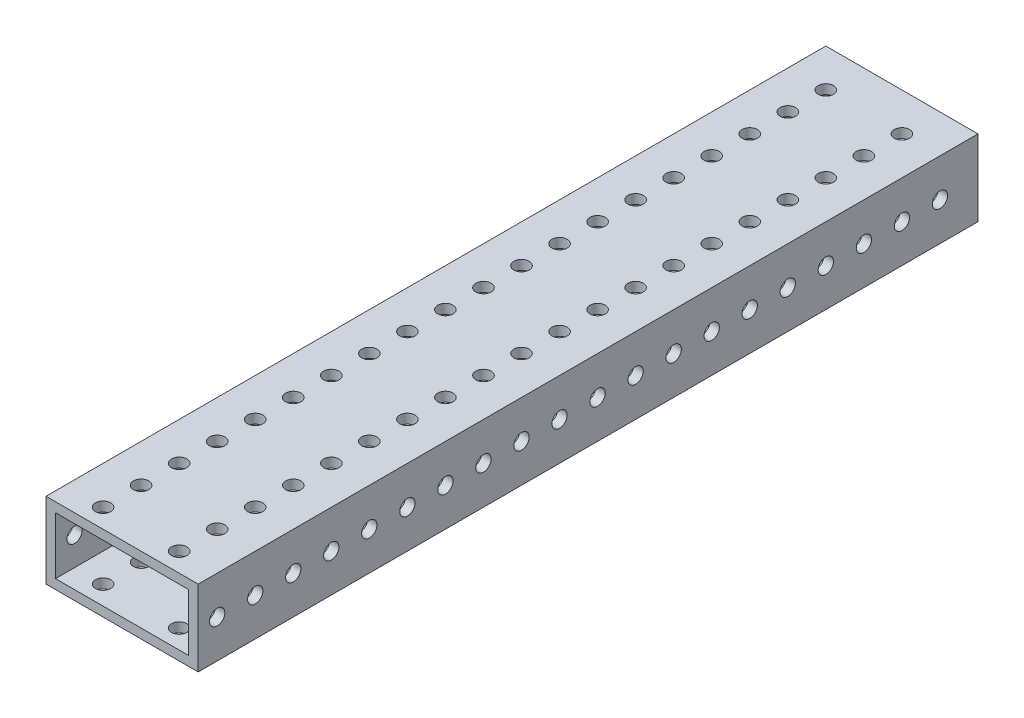
SolidWorks part; units mm, degrees
material "6061-T6 (SS)"
ref_plane "Front Plane" through (0, 0, 0) normal (0, 0, 1) x (1, 0, 0)
ref_plane "Top Plane" through (0, 0, 0) normal (0, 1, 0) x (1, 0, 0)
ref_plane "Right Plane" through (0, 0, 0) normal (1, 0, 0) x (0, 0, -1)
sketch "Sketch1" plane through (0, 0, 0) normal (0, 0, 1) x (1, 0, 0)
  line L0 (-22.225, 9.525) -> (22.225, 9.525)
  line L1 (-25.4, 12.7) -> (25.4, 12.7)
  line L2 (-25.4, 12.7) -> (-25.4, -12.7)
  line L3 (-25.4, -12.7) -> (25.4, -12.7)
  line L4 (25.4, 12.7) -> (25.4, -12.7)
  line L5 (22.225, 9.525) -> (22.225, -9.525)
  line L6 (-22.225, -9.525) -> (22.225, -9.525)
  line L7 (-22.225, 9.525) -> (-22.225, -9.525)
  line L8 (-25.4, 12.7) -> (25.4, -12.7) construction
  line L9 (25.4, 12.7) -> (-25.4, -12.7) construction
  point P5 (0, 0)
  dimension "D1" = 50.8
  dimension "D2" = 25.4
  dimension "D3" = 3.175
extrude "Boss-Extrude1" add sketch "Sketch1" along normal mid plane 368.3
sketch "Sketch5" plane through (-25.4, 0, 0) normal (-1, 0, 0) x (0, 0, 1)
  line L0 (184.15, -12.7) -> (-184.15, -12.7) construction
  line L1 (-184.15, 12.7) -> (-120.65, 12.7)
  line L2 (-184.15, 12.7) -> (-184.15, -12.7)
  line L3 (-184.15, -12.7) -> (-120.65, -12.7)
  line L4 (-120.65, 12.7) -> (-120.65, -12.7)
  dimension "D1" = 63.5
sketch "Sketch6" plane through (25.4, 0, 0) normal (1, 0, 0) x (0, 0, -1)
  line L0 (-184.15, -12.7) -> (-184.15, 12.7) construction
  line L1 (-184.15, 12.7) -> (184.15, 12.7) construction
  circle A0 centre (-177.8, 0) radius 2.5527
  circle A1 centre (-165.1, 0) radius 2.5527
  circle A2 centre (-152.4, 0) radius 2.5527
  circle A3 centre (-139.7, 0) radius 2.5527
  circle A4 centre (-127, 0) radius 2.5527
  circle A5 centre (-114.3, 0) radius 2.5527
  circle A6 centre (-101.6, 0) radius 2.5527
  circle A7 centre (-88.9, 0) radius 2.5527
  circle A8 centre (-76.2, 0) radius 2.5527
  circle A9 centre (-63.5, 0) radius 2.5527
  circle A10 centre (-50.8, 0) radius 2.5527
  circle A11 centre (-38.1, 0) radius 2.5527
  circle A12 centre (-25.4, 0) radius 2.5527
  circle A13 centre (-12.7, 0) radius 2.5527
  circle A14 centre (0, 0) radius 2.5527
  circle A15 centre (12.7, 0) radius 2.5527
  circle A16 centre (25.4, 0) radius 2.5527
  circle A17 centre (38.1, 0) radius 2.5527
  circle A18 centre (50.8, 0) radius 2.5527
  circle A19 centre (63.5, 0) radius 2.5527
  circle A20 centre (76.2, 0) radius 2.5527 construction
  circle A21 centre (88.9, 0) radius 2.5527
  circle A22 centre (101.6, 0) radius 2.5527
  circle A23 centre (114.3, 0) radius 2.5527 construction
  circle A24 centre (127, 0) radius 2.5527 construction
  circle A25 centre (139.7, 0) radius 2.5527 construction
  circle A26 centre (152.4, 0) radius 2.5527 construction
  circle A27 centre (165.1, 0) radius 2.5527 construction
  circle A28 centre (177.8, 0) radius 2.5527 construction
  dimension "D1" = 6.35
  dimension "D2" = 12.7
  dimension "D3" = 5.1054
  dimension "D4" = 29
extrude "Cut-Extrude5" cut sketch "Sketch6" against normal through all
extrude "Cut-Extrude6" cut sketch "Sketch5" against normal through all
sketch "Sketch2" plane through (0, 12.7, 0) normal (0, 1, 0) x (1, 0, 0)
  line L0 (25.4, -184.15) -> (-25.4, -184.15) construction
  line L1 (-25.4, -184.15) -> (-25.4, 120.65) construction
  line L4 (25.4, 184.15) -> (-25.4, 184.15) construction
  circle A0 centre (12.7, -177.8) radius 2.5527
  circle A1 centre (25.4, -171.45) radius 2.5527 construction
  circle A2 centre (-12.7, -177.8) radius 2.5527
  circle A3 centre (-12.7, -165.1) radius 2.5527
  circle A4 centre (12.7, -165.1) radius 2.5527 construction
  circle A5 centre (25.4, -158.75) radius 2.5527 construction
  circle A6 centre (-12.7, -152.4) radius 2.5527
  circle A7 centre (12.7, -152.4) radius 2.5527 construction
  circle A8 centre (25.4, -146.05) radius 2.5527 construction
  circle A9 centre (-12.7, -139.7) radius 2.5527
  circle A10 centre (12.7, -139.7) radius 2.5527 construction
  circle A11 centre (25.4, -133.35) radius 2.5527 construction
  circle A12 centre (-12.7, -127) radius 2.5527
  circle A13 centre (12.7, -127) radius 2.5527 construction
  circle A14 centre (25.4, -120.65) radius 2.5527 construction
  circle A15 centre (-12.7, -114.3) radius 2.5527
  circle A16 centre (12.7, -114.3) radius 2.5527 construction
  circle A17 centre (25.4, -107.95) radius 2.5527 construction
  circle A18 centre (-12.7, -101.6) radius 2.5527
  circle A19 centre (12.7, -101.6) radius 2.5527 construction
  circle A20 centre (25.4, -95.25) radius 2.5527 construction
  circle A21 centre (-12.7, -88.9) radius 2.5527
  circle A22 centre (12.7, -88.9) radius 2.5527 construction
  circle A23 centre (25.4, -82.55) radius 2.5527 construction
  circle A24 centre (-12.7, -76.2) radius 2.5527
  circle A25 centre (12.7, -76.2) radius 2.5527 construction
  circle A26 centre (25.4, -69.85) radius 2.5527 construction
  circle A27 centre (-12.7, -63.5) radius 2.5527
  circle A28 centre (12.7, -63.5) radius 2.5527 construction
  circle A29 centre (25.4, -57.15) radius 2.5527 construction
  circle A30 centre (-12.7, -50.8) radius 2.5527
  circle A31 centre (12.7, -50.8) radius 2.5527 construction
  circle A32 centre (25.4, -44.45) radius 2.5527 construction
  circle A33 centre (-12.7, -38.1) radius 2.5527
  circle A34 centre (12.7, -38.1) radius 2.5527 construction
  circle A35 centre (25.4, -31.75) radius 2.5527 construction
  circle A36 centre (-12.7, -25.4) radius 2.5527
  circle A37 centre (12.7, -25.4) radius 2.5527 construction
  circle A38 centre (25.4, -19.05) radius 2.5527 construction
  circle A39 centre (-12.7, -12.7) radius 2.5527
  circle A40 centre (12.7, -12.7) radius 2.5527 construction
  circle A41 centre (25.4, -6.35) radius 2.5527 construction
  circle A42 centre (-12.7, 0) radius 2.5527
  circle A43 centre (12.7, 0) radius 2.5527 construction
  circle A44 centre (25.4, 6.35) radius 2.5527 construction
  circle A45 centre (-12.7, 12.7) radius 2.5527
  circle A46 centre (12.7, 12.7) radius 2.5527 construction
  circle A47 centre (25.4, 19.05) radius 2.5527 construction
  circle A48 centre (-12.7, 25.4) radius 2.5527
  circle A49 centre (12.7, 25.4) radius 2.5527 construction
  circle A50 centre (25.4, 31.75) radius 2.5527 construction
  circle A51 centre (-12.7, 38.1) radius 2.5527
  circle A52 centre (12.7, 38.1) radius 2.5527 construction
  circle A53 centre (25.4, 44.45) radius 2.5527 construction
  circle A54 centre (-12.7, 50.8) radius 2.5527
  circle A55 centre (12.7, 50.8) radius 2.5527 construction
  circle A56 centre (25.4, 57.15) radius 2.5527 construction
  circle A57 centre (-12.7, 63.5) radius 2.5527
  circle A58 centre (12.7, 63.5) radius 2.5527 construction
  circle A59 centre (25.4, 69.85) radius 2.5527 construction
  circle A60 centre (-12.7, 76.2) radius 2.5527 construction
  circle A61 centre (12.7, 76.2) radius 2.5527 construction
  circle A62 centre (25.4, 82.55) radius 2.5527 construction
  circle A63 centre (-12.7, 88.9) radius 2.5527
  circle A64 centre (12.7, 88.9) radius 2.5527 construction
  circle A65 centre (25.4, 95.25) radius 2.5527 construction
  circle A66 centre (-12.7, 101.6) radius 2.5527
  circle A67 centre (12.7, 101.6) radius 2.5527 construction
  circle A68 centre (25.4, 107.95) radius 2.5527 construction
  circle A69 centre (-12.7, 114.3) radius 2.5527 construction
  circle A70 centre (12.7, 114.3) radius 2.5527 construction
  circle A71 centre (25.4, 120.65) radius 2.5527 construction
  circle A72 centre (-12.7, 127) radius 2.5527 construction
  circle A73 centre (12.7, 127) radius 2.5527 construction
  circle A74 centre (25.4, 133.35) radius 2.5527 construction
  circle A75 centre (-12.7, 139.7) radius 2.5527
  circle A76 centre (12.7, 139.7) radius 2.5527 construction
  circle A77 centre (25.4, 146.05) radius 2.5527 construction
  circle A78 centre (-12.7, 152.4) radius 2.5527
  circle A79 centre (12.7, 152.4) radius 2.5527 construction
  circle A80 centre (25.4, 158.75) radius 2.5527 construction
  circle A81 centre (-12.7, 165.1) radius 2.5527
  circle A82 centre (12.7, 165.1) radius 2.5527 construction
  circle A83 centre (25.4, 171.45) radius 2.5527 construction
  circle A84 centre (-12.7, 177.8) radius 2.5527 construction
  circle A85 centre (12.7, 177.8) radius 2.5527 construction
  circle A86 centre (25.4, 184.15) radius 2.5527 construction
  circle A87 centre (-12.7, 190.5) radius 2.5527
  circle A88 centre (12.7, 190.5) radius 2.5527 construction
  circle A89 centre (25.4, 196.85) radius 2.5527 construction
  circle A90 centre (-12.7, 203.2) radius 2.5527
  circle A91 centre (12.7, 203.2) radius 2.5527 construction
  circle A92 centre (25.4, 209.55) radius 2.5527 construction
  circle A93 centre (-12.7, 215.9) radius 2.5527
  circle A94 centre (12.7, 215.9) radius 2.5527 construction
  circle A95 centre (25.4, 222.25) radius 2.5527 construction
  circle A96 centre (-12.7, 228.6) radius 2.5527
  circle A97 centre (12.7, 228.6) radius 2.5527 construction
  circle A98 centre (25.4, 234.95) radius 2.5527 construction
  circle A99 centre (-12.7, 241.3) radius 2.5527
  circle A100 centre (12.7, 241.3) radius 2.5527 construction
  circle A101 centre (25.4, 247.65) radius 2.5527 construction
  circle A108 centre (-12.7, 266.7) radius 2.5527 [skipped]
  circle A109 centre (12.7, 266.7) radius 2.5527 [skipped]
  circle A110 centre (25.4, 273.05) radius 2.5527 [skipped]
  circle A111 centre (-12.7, 254) radius 2.5527 [skipped]
  circle A112 centre (12.7, 254) radius 2.5527 [skipped]
  circle A113 centre (25.4, 260.35) radius 2.5527 [skipped]
  circle A114 centre (25.4, 260.35) radius 2.5527 construction
  circle A115 centre (12.7, 254) radius 2.5527 construction
  circle A116 centre (-12.7, 254) radius 2.5527
  circle A117 centre (25.4, 273.05) radius 2.5527 construction
  circle A118 centre (12.7, 266.7) radius 2.5527 construction
  circle A119 centre (-12.7, 266.7) radius 2.5527
  circle A120 centre (25.4, 285.75) radius 2.5527 construction
  circle A121 centre (12.7, 279.4) radius 2.5527 construction
  circle A122 centre (-12.7, 279.4) radius 2.5527
  circle A123 centre (25.4, 298.45) radius 2.5527 construction
  circle A124 centre (12.7, 292.1) radius 2.5527 construction
  circle A125 centre (-12.7, 292.1) radius 2.5527
  circle A126 centre (25.4, 311.15) radius 2.5527 construction
  circle A127 centre (12.7, 304.8) radius 2.5527 construction
  circle A128 centre (-12.7, 304.8) radius 2.5527
  circle A129 centre (25.4, 323.85) radius 2.5527 construction
  circle A130 centre (12.7, 317.5) radius 2.5527 construction
  circle A131 centre (-12.7, 317.5) radius 2.5527
  circle A132 centre (25.4, 336.55) radius 2.5527 construction
  circle A133 centre (12.7, 330.2) radius 2.5527 construction
  circle A134 centre (-12.7, 330.2) radius 2.5527
  circle A135 centre (25.4, 349.25) radius 2.5527 construction
  circle A136 centre (12.7, 342.9) radius 2.5527 construction
  circle A137 centre (-12.7, 342.9) radius 2.5527
  circle A138 centre (25.4, 361.95) radius 2.5527 construction
  circle A139 centre (12.7, 355.6) radius 2.5527 construction
  circle A140 centre (-12.7, 355.6) radius 2.5527
  circle A141 centre (25.4, 374.65) radius 2.5527 construction
  circle A142 centre (12.7, 368.3) radius 2.5527 construction
  circle A143 centre (-12.7, 368.3) radius 2.5527
  circle A144 centre (25.4, 387.35) radius 2.5527 construction
  circle A145 centre (12.7, 381) radius 2.5527 construction
  circle A146 centre (-12.7, 381) radius 2.5527
  circle A147 centre (25.4, 400.05) radius 2.5527 construction
  circle A148 centre (12.7, 393.7) radius 2.5527 construction
  circle A149 centre (-12.7, 393.7) radius 2.5527
  circle A150 centre (25.4, 412.75) radius 2.5527 construction
  circle A151 centre (12.7, 406.4) radius 2.5527 construction
  circle A152 centre (-12.7, 406.4) radius 2.5527
  circle A153 centre (12.7, -165.1) radius 2.5527
  circle A154 centre (12.7, -152.4) radius 2.5527
  circle A155 centre (12.7, -139.7) radius 2.5527
  circle A156 centre (12.7, -127) radius 2.5527
  circle A157 centre (12.7, -114.3) radius 2.5527
  circle A158 centre (12.7, -101.6) radius 2.5527
  circle A159 centre (12.7, -88.9) radius 2.5527
  circle A160 centre (12.7, -76.2) radius 2.5527
  circle A161 centre (12.7, -63.5) radius 2.5527
  circle A162 centre (12.7, -50.8) radius 2.5527
  circle A163 centre (12.7, -38.1) radius 2.5527
  circle A164 centre (12.7, -25.4) radius 2.5527
  circle A165 centre (12.7, -12.7) radius 2.5527
  circle A166 centre (12.7, 0) radius 2.5527
  circle A167 centre (12.7, 12.7) radius 2.5527
  circle A168 centre (12.7, 25.4) radius 2.5527
  circle A169 centre (12.7, 38.1) radius 2.5527
  circle A170 centre (12.7, 50.8) radius 2.5527
  circle A171 centre (12.7, 63.5) radius 2.5527
  circle A172 centre (12.7, 76.2) radius 2.5527 construction
  circle A173 centre (12.7, 88.9) radius 2.5527
  circle A174 centre (12.7, 101.6) radius 2.5527
  circle A175 centre (12.7, 114.3) radius 2.5527 construction
  circle A176 centre (12.7, 127) radius 2.5527 construction
  circle A177 centre (12.7, 139.7) radius 2.5527
  circle A178 centre (12.7, 152.4) radius 2.5527
  circle A179 centre (12.7, 165.1) radius 2.5527
  circle A180 centre (12.7, 177.8) radius 2.5527 construction
  circle A181 centre (12.7, 190.5) radius 2.5527
  circle A182 centre (12.7, 203.2) radius 2.5527
  circle A183 centre (12.7, 215.9) radius 2.5527
  circle A184 centre (12.7, 228.6) radius 2.5527
  circle A185 centre (12.7, 241.3) radius 2.5527
  circle A186 centre (12.7, 254) radius 2.5527
  circle A187 centre (12.7, 266.7) radius 2.5527
  circle A188 centre (12.7, 279.4) radius 2.5527
  circle A189 centre (12.7, 292.1) radius 2.5527
  circle A190 centre (12.7, 304.8) radius 2.5527
  circle A191 centre (12.7, 317.5) radius 2.5527
  circle A192 centre (12.7, 330.2) radius 2.5527
  circle A193 centre (12.7, 342.9) radius 2.5527
  circle A194 centre (12.7, 355.6) radius 2.5527
  circle A195 centre (12.7, 368.3) radius 2.5527
  circle A196 centre (12.7, 381) radius 2.5527
  circle A197 centre (12.7, 393.7) radius 2.5527
  circle A198 centre (12.7, 406.4) radius 2.5527
  circle A199 centre (12.7, 419.1) radius 2.5527
  circle A200 centre (12.7, 431.8) radius 2.5527
  circle A201 centre (12.7, 444.5) radius 2.5527
  dimension "D2" = 5.1054
  dimension "D4" = 50
  dimension "D9" = 12.7
  dimension "D10" = 12.7
  dimension "D11" = 6.35
  dimension "D1" = 6.35
  dimension "D3" = 38.1
  dimension "D6" = 12.7
  dimension "D7" = 57.15
  dimension "D5" = 36
  dimension "D8" = 14
extrude "Cut-Extrude1" cut sketch "Sketch2" against normal through all
sketch "Sketch7" plane through (-25.4, 0, 0) normal (-1, 0, 0) x (0, 0, 1)
  line L5 (-120.65, 12.7) -> (-76.2, 12.7)
  line L6 (-120.65, 12.7) -> (-120.65, -12.7)
  line L7 (-120.65, -12.7) -> (-76.2, -12.7)
  line L8 (-76.2, 12.7) -> (-76.2, -12.7)
  dimension "D1" = 44.45
extrude "Cut-Extrude7" cut sketch "Sketch7" against normal through all
